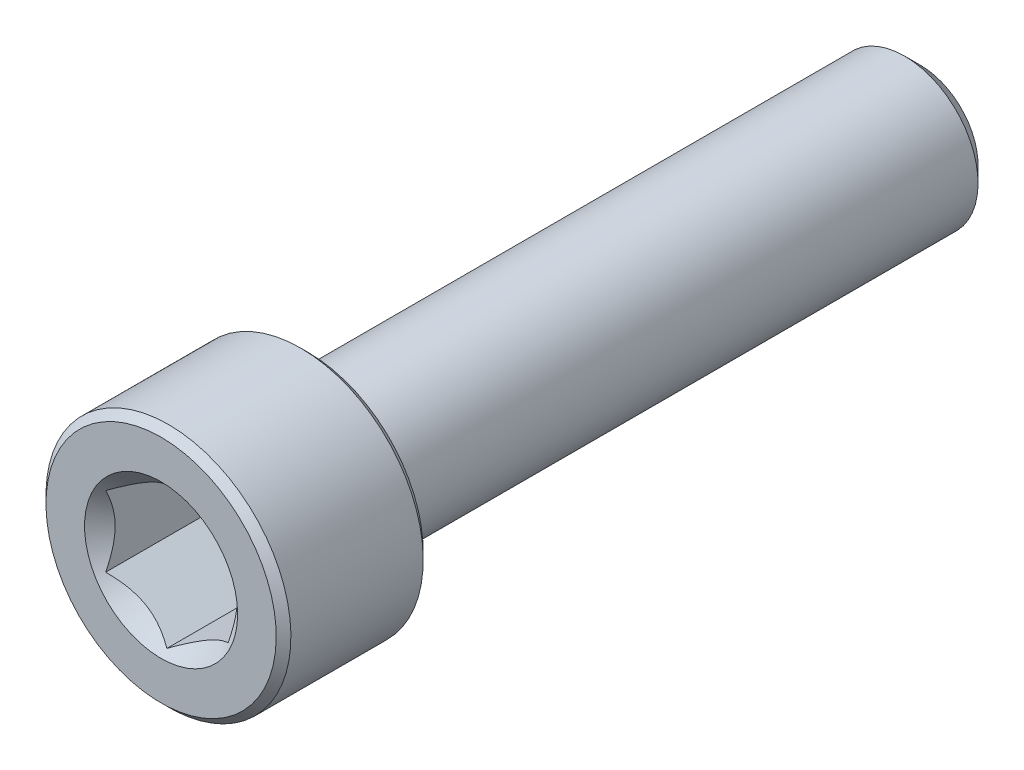
SolidWorks part; units mm, degrees
ref_plane "Front Plane" through (0, 0, 0) normal (0, 0, 1) x (1, 0, 0)
ref_plane "Top Plane" through (0, 0, 0) normal (0, 1, 0) x (1, 0, 0)
ref_plane "Right Plane" through (0, 0, 0) normal (1, 0, 0) x (0, 0, -1)
sketch "Sketch1" plane through (0, 0, 0) normal (1, 0, 0) x (0, 0, -1)
  line L0 (-15.5, 0) -> (15.5, 0) construction
  line L1 (15.5, 0) -> (15.5, 2.3505) construction
  line L2 (15.5, 2.3505) -> (14.8505, 3) construction
  line L3 (14.8505, 3) -> (14.75, 3) construction
  line L4 (14.75, 3) -> (-9.5, 3) construction
  line L5 (-9.5, 3) -> (-9.5, 5) construction
  line L6 (-9.5, 5) -> (-15.5, 5) construction
  line L7 (-15.5, 5) -> (-15.5, 0) construction
  line L8 (15.5, 2.3505) -> (15.5, 3) construction
  line L9 (15.4375, 3.1083) -> (15.9375, 2.2422) construction
  line L10 (15.9375, 2.2422) -> (16.4375, 3.1083) construction
  line L11 (16.4375, 3.1083) -> (15.4375, 3.1083) construction
  line L12 (15.9375, 3.1083) -> (15.9375, 3) construction
  line L13 (15.9375, 2.2422) -> (15.9375, 2.3505) construction
  line L14 (15.875, 2.3505) -> (16, 2.3505) construction
  line L15 (15.5, 3) -> (16.375, 3) construction
  line L16 (15.4688, 3.0541) -> (16.4062, 3.0541) construction
  line L17 (15.5, 0) -> (15.5, -3) construction
  line L18 (-9.8, 5) -> (-9.5, 4.7) construction
  line L19 (-15.2, 5) -> (-15.5, 4.7) construction
  line L20 (-9.5, 3) -> (-9.5, 0) construction
  line L21 (-9.5, 1.5) -> (-1.1667, 1.5) construction
  line L22 (-1.1667, 1.5) -> (7.1667, 1.5) construction
  line L23 (7.1667, 1.5) -> (15.5, 1.5) construction
  line L24 (-1.1667, 1.5) -> (-1.1667, 3) construction
  line L25 (-1.1667, 3) -> (-1.1667, 5) construction
  line L26 (7.1667, 1.5) -> (7.1667, 5) construction
  point P0 (-15.5, 2.5)
  point P3 (13, 3)
  point P4 (0, 0)
  point P18 (7.1667, 3)
  point P22 (15.9375, 2.3505)
  point P24 (14.75, 3)
  point P25 (15.9375, 3)
  point P28 (15.9375, 3.0541)
  point P29 (13, -3)
  point P30 (-1.1667, 3)
  point P31 (-12.5, 5)
  point P37 (-10.55, 5)
  point P38 (-15.05, 5)
  point P45 (-1.1667, 1.5)
  point P46 (7.1667, 1.5)
  dimension "D2" = 0.125
  dimension "D7" = 0.3
  dimension "D8" = 0.3
  dimension "D9" = 0.3
  dimension "D10" = 0.15
  dimension "D11" = 0.75
  dimension "Drive Size" = 5
  dimension "Head Diameter" = 10
  dimension "Head Height" = 6
  dimension "Thread Pitch" = 1
  dimension "Thread Size" = 6
  dimension "Length" = 25
  dimension "D12" = 0.75
  dimension "D4" = 2.5
  dimension "D3" = 45
sketch "Sketch2" plane through (0, 0, 0) normal (1, 0, 0) x (0, 0, -1)
  line L0 (-15.5, 0) -> (-15.5, 4.7)
  line L1 (-15.2, 5) -> (-9.8, 5)
  line L2 (-9.5, 4.7) -> (-9.5, 3.3)
  line L4 (14.8505, 3) -> (15.5, 2.3505)
  line L5 (15.5, 2.3505) -> (15.5, 0)
  line L6 (-9.5, 5) -> (-15.5, 5) construction
  line L7 (15.5, 0) -> (-15.5, 0)
  line L8 (-15.2, 5) -> (-15.5, 4.7) construction
  line L10 (-15.2, 5) -> (-15.5, 4.7)
  line L14 (-9.8, 5) -> (-9.5, 4.7) construction
  line L16 (-9.8, 5) -> (-9.5, 4.7)
  line L17 (-9.5, 3) -> (-9.5, 5) construction
  line L19 (-9.2, 3) -> (14.8505, 3)
  line L20 (14.75, 3) -> (-9.5, 3) construction
  arc A1 (-9.5, 3.3) -> (-9.2, 3) centre (-9.2, 3.3) ccw
  dimension "D3" = 0.3
revolve "Revolve1" add sketch "Sketch2" angle 360 about L7
sketch "Sketch3" plane through (0, 0, 15.5) normal (0, 0, 1) x (1, 0, 0)
  line L1 (2.5, -1.4434) -> (2.5, 1.4434)
  line L2 (2.5, 1.4434) -> (0, 2.8868)
  line L3 (0, 2.8868) -> (-2.5, 1.4434)
  line L4 (-2.5, 1.4434) -> (-2.5, -1.4434)
  line L5 (-2.5, -1.4434) -> (0, -2.8868)
  line L6 (0, -2.8868) -> (2.5, -1.4434)
  circle A0 centre (0, 0) radius 2.5 construction
  circle A1 centre (0, 0) radius 5 construction
  circle A2 centre (0, 0) radius 5 construction
  circle A3 centre (0, 0) radius 2.8868 construction
  point P13 (0, 0)
extrude "Cut-Extrude1" cut sketch "Sketch3" against normal offset from surface (5 mm away) 1 up to face at (0, 4.7, 9.5)
sketch "Sketch4" plane through (0, 0, 15.5) normal (0, 0, 1) x (1, 0, 0)
  circle A0 centre (0, 0) radius 3.125
  dimension "D1" = 6.25
extrude "Cut-Extrude2" cut sketch "Sketch4" against normal up to vertex (3 mm away) draft 45 up to point (0, 5, 12.5)
sketch "Sketch11" plane through (0, 0, 0) normal (1, 0, 0) x (0, 0, -1)
  line L0 (-15.5, 0) -> (15.5, 0) construction
  line L1 (-15.5, 0) -> (15.5, 0) construction
  line L2 (-4.8125, 0) -> (-4.8125, 3) construction
  line L3 (14.75, 3) -> (-9.5, 3) construction
  line L4 (10.8125, 0) -> (10.8125, 3) construction
  line L6 (15.5, 2.3505) -> (15.5, 3) construction
  point P2 (-4.8125, 0)
  point P3 (10.8125, 0)
  dimension "D1" = 4.6875
  dimension "D2" = 4.6875
sketch "Sketch6" [suppressed] plane through (0, 0, -15.5) normal (0, 0, -1) x (-1, 0, 0)
  circle A0 centre (0, 0) radius 3
curve "Helix/Spiral1" [suppressed] pitch 1 height 26 turns 26
sketch "Sketch10" [suppressed] plane through (0, 0, 0) normal (1, 0, 0) x (0, 0, -1)
  line L0 (-9.2, -5) -> (-9.2, 5)
  line L5 (-15.5, 0) -> (15.5, 0) construction
  line L6 (-9.2, 3) -> (-9.2, -3) construction
  point P3 (-9.2, 0)
split "Split1" [suppressed] bodies to split 106
sketch "Sketch7" [suppressed] plane through (0, 0, 0) normal (1, 0, 0) x (0, 0, -1)
  line L0 (15.4688, 3.0541) -> (16.4062, 3.0541)
  line L1 (16.4062, 3.0541) -> (16, 2.3505)
  line L2 (16, 2.3505) -> (15.875, 2.3505)
  line L3 (15.875, 2.3505) -> (15.4688, 3.0541)
sweep "Cut-Sweep1" [suppressed] cut profiles "Sketch7" path "Helix/Spiral1"
sketch "Sketch8" [suppressed] plane through (0, 0, 0) normal (1, 0, 0) x (0, 0, -1)
  line L0 (-9.5, 0) -> (-9.5, 3)
  line L1 (-9.2, -3) -> (-9.2, 3) construction
  line L2 (-9.5, 3) -> (-9.2, 3)
  line L4 (-9.2, 3) -> (-7.4679, 0)
  line L5 (-7.4679, 0) -> (-9.5, 0)
  line L6 (14.75, 3) -> (-9.5, 3) construction
  line L7 (-15.5, 0) -> (15.5, 0) construction
  dimension "D1" = 60
revolve "Revolve2" [suppressed] add sketch "Sketch8" angle 360 about L5
ref_plane "Plane1" [suppressed] through (0, 0, 15.5) normal (0, 0, 1) x (1, 0, 0)
sketch "Sketch12" [suppressed] plane through (0, 0, 15.5) normal (0, 0, 1) x (1, 0, 0)
  line L0 (0, 0) -> (0.1745, 4.997) construction
  line L1 (0, 0) -> (-0.1745, 4.997) construction
  line L2 (0, 4.875) -> (0, 5.125) construction
  line L3 (-0.3025, 5.125) -> (0.3025, 5.125)
  line L4 (-0.3025, 5.125) -> (-0.0897, 4.9122)
  line L5 (0.0897, 4.9122) -> (0.3025, 5.125)
  circle A0 centre (0, 0) radius 5 construction
  arc A1 (-0.0897, 4.9122) -> (0.0897, 4.9122) centre (0, 5.0019) ccw
  point P9 (0, 5.125)
  point P13 (0, 5)
  dimension "D2" = 0.125
  dimension "D1" = 4
extrude "Cut-Extrude3" [suppressed] cut sketch "Sketch12" against normal blind 4.8
pattern_circular "CirPattern1" [suppressed] count 72 over 360 about axis through (0, 0, 15.5) along (0, 0, -1) of bodies 118
equation "\"D2@Sketch1\" = \"Thread Pitch@Sketch1\" / 8"
equation "\"D4@Helix/Spiral1\" = \"Thread Pitch@Sketch1\""
equation "\"D7@Sketch1\" = \"Head Height@Sketch1\" * .05"
equation "\"D8@Sketch1\"=\"D7@Sketch1\""
equation "\"D9@Sketch1\"=\"D7@Sketch1\""
equation "\"D10@Sketch1\"=\"D7@Sketch1\"/2"
equation "\"D11@Sketch1\"=\"D10@Sketch1\"*5"
equation "\"D4@Sketch1\"=\"Thread Pitch@Sketch1\"*2.5"
equation "\"D12@Sketch1\"=\"Thread Pitch@Sketch1\"*.75"
equation "\"D3@Helix/Spiral1\"=\"Length@Sketch1\"+\"Thread Pitch@Sketch1\""
equation "\"D3@Sketch2\" = \"Thread Size@Sketch1\" * 0.05"
equation "\"D1@Sketch11\"=\"Length@Sketch1\"*0.1875"
equation "\"D2@Sketch11\"=\"D1@Sketch11\""
equation "\"D2@Sketch12\"=\"Head Diameter@Sketch1\"*.0125"
equation "\"D1@Cut-Extrude3\"=\"Head Height@Sketch1\"*.8"
equation "\"D1@CirPattern1\"=\"D3@CirPattern1\"/(1.25*\"D1@Sketch12\")"
equation "\"D1@Sketch4\"=\"Drive Size@Sketch1\"*1.25"
